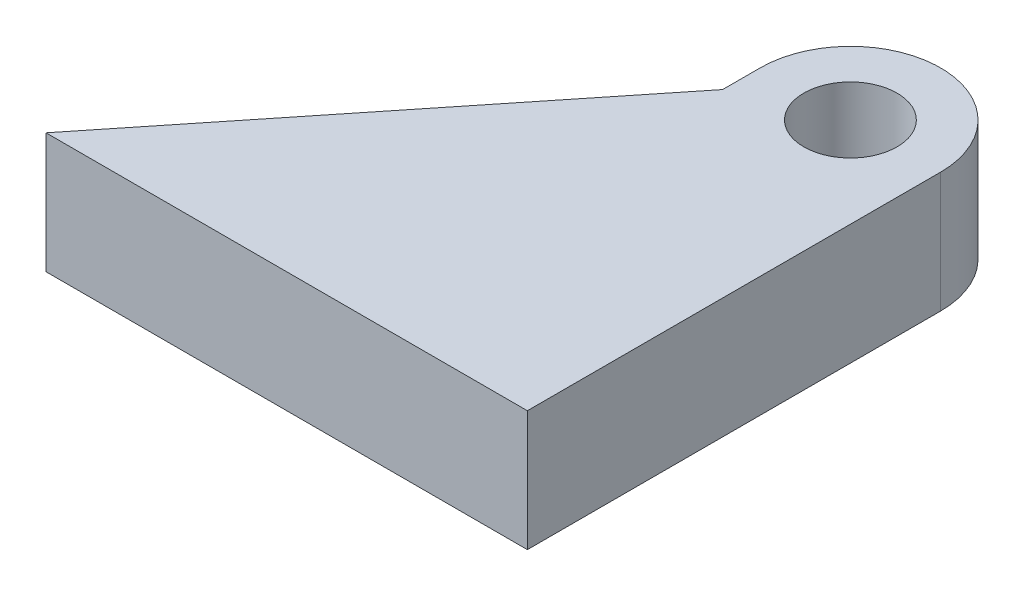
SolidWorks part; units mm, degrees
ref_plane "Front Plane" through (0, 0, 0) normal (0, 0, 1) x (1, 0, 0)
ref_plane "Top Plane" through (0, 0, 0) normal (0, 1, 0) x (1, 0, 0)
ref_plane "Right Plane" through (0, 0, 0) normal (1, 0, 0) x (0, 0, -1)
sketch "Sketch1" plane through (0, 0, 0) normal (0, 1, 0) x (1, 0, 0)
  line L1 (-15, 0) -> (-15.0017, -6.2425)
  line L2 (-65.0017, -68.6925) -> (15, -68.6925)
  line L4 (-65.0017, -68.6925) -> (-15.0017, -6.2425)
  line L6 (15, -68.6925) -> (15, 0)
  circle A0 centre (0, 0) radius 7.75
  arc A1 (15, 0) -> (-15, 0) centre (0, -0.004) ccw
  dimension "D1" = 15.5
  dimension "D3" = 80
extrude "Boss-Extrude1" add sketch "Sketch1" along normal blind 20
sketch "Sketch2" plane through (0, 20, 0) normal (0, 1, 0) x (1, 0, 0)
  line L0 (-65.0017, -68.6925) -> (15, -68.6925) construction
  line L1 (15, 0) -> (-15, 0)
  line L2 (15, 0) -> (15, -68.6925)
  line L3 (15, -68.6925) -> (-15, -68.6925)
  line L4 (-15, 0) -> (-15, -68.6925)
  dimension "D1" = 30
ref_point "Point1"
